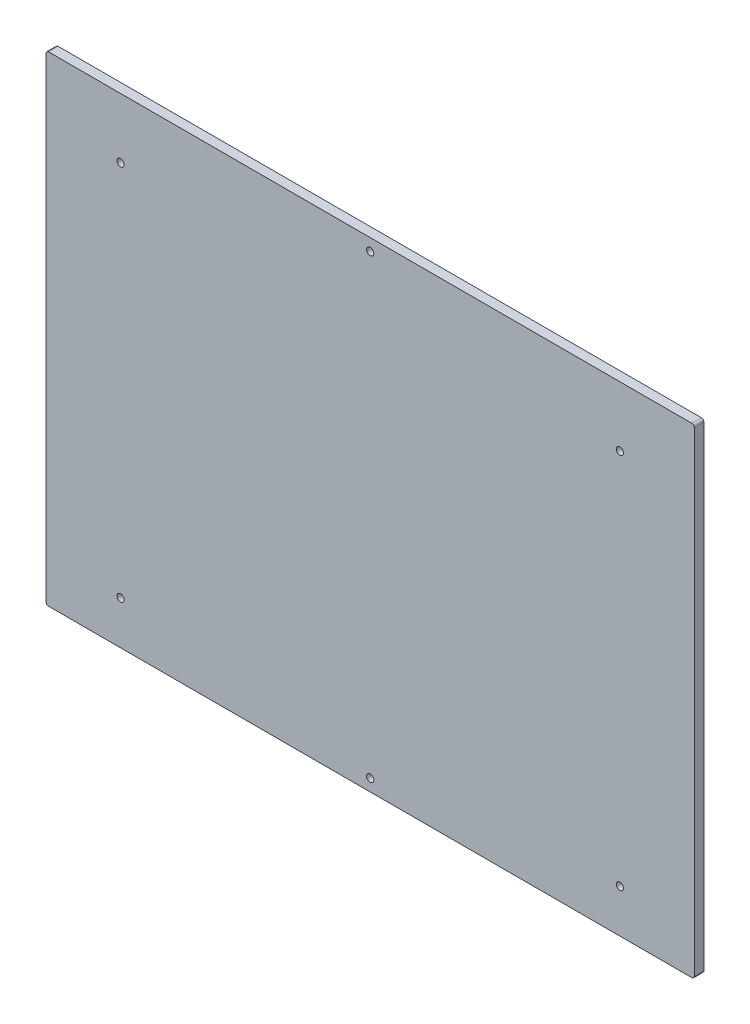
SolidWorks part; units mm, degrees
ref_plane "前视基准面" through (0, 0, 0) normal (0, 0, 1) x (1, 0, 0)
ref_plane "上视基准面" through (0, 0, 0) normal (0, 1, 0) x (1, 0, 0)
ref_plane "右视基准面" through (0, 0, 0) normal (1, 0, 0) x (0, 0, -1)
sketch "草图1" plane through (0, 0, 0) normal (0, 0, 1) x (1, 0, 0)
  line L1 (-135, -100) -> (135, -100)
  line L2 (-135, -100) -> (-135, 100)
  line L3 (-135, 100) -> (135, 100)
  line L4 (135, -100) -> (135, 100)
  line L5 (-135, -100) -> (135, 100) construction
  line L6 (-135, 100) -> (135, -100) construction
  point P1 (0, 0)
  dimension "D1" = 270
  dimension "D2" = 200
base flange "基体-法兰1" sketch "草图1" thickness 4 reverse thickness direction no parameters "D1"=10
sketch "草图6" plane through (0, 0, 0) normal (0, 0, 1) x (1, 0, 0)
  line L0 (135, 100) -> (-135, 100) construction
  circle A0 centre (0, 95) radius 1.5
  dimension "D1" = 3
  dimension "D2" = 5
extrude "切除-拉伸1" cut sketch "草图6" against normal blind 10 normal cut yes
mirror "镜向1" about plane through (0, 0, 0) normal (0, 1, 0) of "切除-拉伸1"
fillet "圆角1" radius 1 4 edges at (135, 100, -2) (135, -100, -2) (-135, -100, -2) (-135, 100, -2)
sketch "草图7" plane through (0, 0, -4) normal (0, 0, -1) x (-1, 0, 0)
  line L0 (-134, 100) -> (134, 100) construction
  circle A0 centre (-104, 75) radius 1.5
  dimension "D2" = 3
  dimension "D1" = 104
  dimension "D3" = 25
extrude "切除-拉伸2" cut sketch "草图7" against normal blind 10 normal cut yes
mirror "镜向2" about plane through (0, 0, 0) normal (1, 0, 0) of "切除-拉伸2"
sketch "草图8" plane through (0, 0, -4) normal (0, 0, -1) x (-1, 0, 0)
  line L0 (134, -100) -> (-134, -100) construction
  circle A0 centre (-104, -82) radius 1.5
  point P6 (-201.1264, -6.7381)
  dimension "D1" = 3
  dimension "D2" = 18
extrude "切除-拉伸3" cut sketch "草图8" against normal blind 10 normal cut yes
mirror "镜向3" about plane through (0, 0, 0) normal (1, 0, 0) of "切除-拉伸3"
sketch "折弯-线1" [suppressed] plane through (0, 0, 0) normal (0, 1, 0) x (1, 0, 0)
sketch "边界框1" [suppressed] plane through (0, 0, 0) normal (0, 1, 0) x (1, 0, 0)
sheet metal parameters "钣金1" thickness 4 parameters "D1"=10
flat pattern "平板型式1" [suppressed]
sketch "折弯-线2" plane through (0, 0, 0) normal (0, 1, 0) x (1, 0, 0)
sketch3d "边界框2" [suppressed]
  line L0 (136, -75, 0) -> (-136, -75, 0) construction
  line L1 (136, 75, 0) -> (-136, 75, 0) construction
  line L2 (136, -75, 0) -> (136, 75, 0) construction
  line L3 (-136, -75, 0) -> (-136, 75, 0) construction
sheet metal parameters "钣金2" thickness 4 parameters "D1"=10
flat pattern "平板型式1"
sketch "折弯-线2" plane through (0, 0, 0) normal (0, 1, 0) x (1, 0, 0)
sketch3d "边界框2" [suppressed]
  line L0 (-136, -75, 0) -> (136, -75, 0) construction
  line L1 (-136, 75, 0) -> (136, 75, 0) construction
  line L2 (-136, -75, 0) -> (-136, 75, 0) construction
  line L3 (136, -75, 0) -> (136, 75, 0) construction
sheet metal parameters "钣金3" thickness 4 parameters "D1"=10
flat pattern "平板型式1"
sketch "折弯-线2" plane through (0, 0, 0) normal (0, 1, 0) x (1, 0, 0)
sketch3d "边界框2" [suppressed]
  line L0 (-135, -100, 0) -> (135, -100, 0) construction
  line L1 (-135, 100, 0) -> (135, 100, 0) construction
  line L2 (-135, -100, 0) -> (-135, 100, 0) construction
  line L3 (135, -100, 0) -> (135, 100, 0) construction
sheet metal parameters "钣金4" thickness 4 parameters "D1"=10
flat pattern "平板型式1"
sketch "折弯-线2" plane through (0, 0, 0) normal (0, 1, 0) x (1, 0, 0)
sketch3d "边界框2" [suppressed]
  line L0 (-135, -100, 0) -> (135, -100, 0) construction
  line L1 (-135, 100, 0) -> (135, 100, 0) construction
  line L2 (-135, -100, 0) -> (-135, 100, 0) construction
  line L3 (135, -100, 0) -> (135, 100, 0) construction
sheet metal parameters "钣金5" thickness 4 parameters "D1"=10
flat pattern "平板型式1"
sketch "折弯-线2" plane through (0, 0, 0) normal (0, 1, 0) x (1, 0, 0)
sketch3d "边界框2" [suppressed]
  line L0 (-135, -100, 0) -> (135, -100, 0) construction
  line L1 (-135, 100, 0) -> (135, 100, 0) construction
  line L2 (-135, -100, 0) -> (-135, 100, 0) construction
  line L3 (135, -100, 0) -> (135, 100, 0) construction
sheet metal parameters "钣金6" thickness 4 parameters "D1"=10
flat pattern "平板型式1"
sketch "折弯-线2" plane through (0, 0, 0) normal (0, 1, 0) x (1, 0, 0)
sketch3d "边界框2" [suppressed]
  line L0 (-135, -100, 0) -> (135, -100, 0) construction
  line L1 (-135, 100, 0) -> (135, 100, 0) construction
  line L2 (-135, -100, 0) -> (-135, 100, 0) construction
  line L3 (135, -100, 0) -> (135, 100, 0) construction
sheet metal parameters "钣金7" thickness 4 parameters "D1"=10
flat pattern "平板型式1"
sketch "折弯-线2" plane through (0, 0, 0) normal (0, 1, 0) x (1, 0, 0)
sketch3d "边界框2" [suppressed]
  line L0 (-135, -100, 0) -> (135, -100, 0) construction
  line L1 (-135, 100, 0) -> (135, 100, 0) construction
  line L2 (-135, -100, 0) -> (-135, 100, 0) construction
  line L3 (135, -100, 0) -> (135, 100, 0) construction
